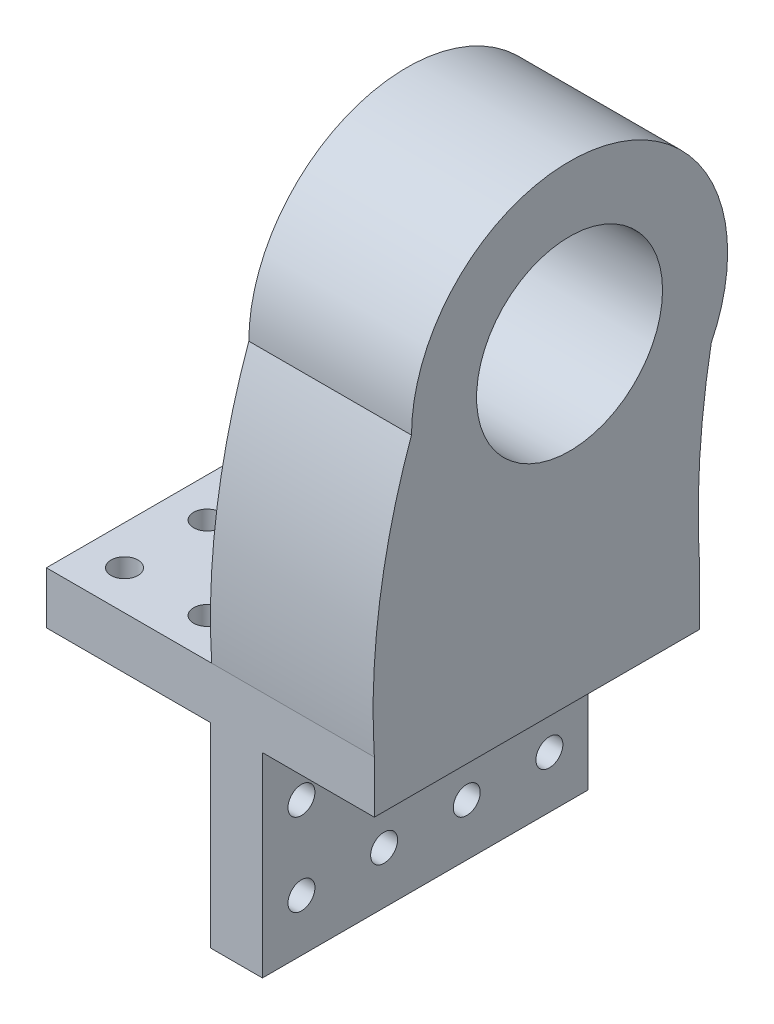
SolidWorks part; units mm, degrees
ref_plane "Alzado" through (0, 0, 0) normal (0, 0, 1) x (1, 0, 0)
ref_plane "Planta" through (0, 0, 0) normal (0, 1, 0) x (1, 0, 0)
ref_plane "Vista lateral" through (0, 0, 0) normal (1, 0, 0) x (0, 0, -1)
sketch "Croquis1" plane through (0, 0, 0) normal (0, 1, 0) x (1, 0, 0)
  line L1 (-25.2, -25) -> (25.2, -25)
  line L2 (-25.2, -25) -> (-25.2, 25)
  line L3 (-25.2, 25) -> (25.2, 25)
  line L4 (25.2, -25) -> (25.2, 25)
  line L5 (-25.2, -25) -> (25.2, 25) construction
  line L6 (-25.2, 25) -> (25.2, -25) construction
  point P0 (0, 0)
  dimension "D1" = 50.4
  dimension "D2" = 50
extrude "Saliente-Extruir1" add sketch "Croquis1" along normal blind 8
sketch "Croquis2" plane through (25.2, 0, 0) normal (1, 0, 0) x (0, 0, -1)
  line L0 (-25, 8) -> (25, 8) construction
  line L1 (-25, 8) -> (-25, 0) construction
  line L2 (-25, 8) -> (25, 8)
  circle A0 centre (5, 48) radius 14.29
  arc A1 (26.7814, 37.2494) -> (-19.29, 48) centre (5, 48) ccw
  arc A2 (-25, 8) -> (-19.29, 48) centre (74.8101, 14.1597) cw
  arc A3 (25, 8) -> (26.7814, 37.2494) centre (144.7726, 15.3844) cw
  dimension "D1" = 28.58
  dimension "D2" = 10
  dimension "D3" = 40
  dimension "D5" = 100
  dimension "D6" = 120
  dimension "D4" = 30
extrude "Saliente-Extruir2" add sketch "Croquis2" against normal blind 25
sketch "Croquis3" plane through (0, 0, 0) normal (0, -1, 0) x (1, 0, 0)
  line L0 (-25.2, 25) -> (25.2, 25) construction
  line L1 (0, 25) -> (8, 25)
  line L2 (0, 25) -> (0, -25)
  line L3 (0, -25) -> (8, -25)
  line L4 (8, 25) -> (8, -25)
  line L5 (25.2, -25) -> (-25.2, -25) construction
  dimension "D1" = 8
extrude "Saliente-Extruir3" add sketch "Croquis3" along normal blind 30
sketch "Croquis4" plane through (0, 8, 0) normal (0, 1, 0) x (1, 0, 0)
  line L0 (-25.2, -25) -> (0.2, -25) construction
  line L1 (-25.2, 25) -> (-25.2, -25) construction
  circle A0 centre (-19.2, -19) radius 2.07
  circle A1 centre (-19.2, -6.3) radius 2.07
  circle A2 centre (-19.2, 6.4) radius 2.07
  circle A3 centre (-19.2, 19.1) radius 2.07
  circle A4 centre (-6.5, -19) radius 2.07
  circle A5 centre (-6.5, 6.4) radius 2.07
  circle A6 centre (-6.5, -6.3) radius 2.07
  circle A7 centre (-6.5, 19.1) radius 2.07
  dimension "D1" = 4.14
  dimension "D2" = 6
  dimension "D3" = 6
  dimension "D4" = 4
  dimension "D5" = 2
extrude "Cortar-Extruir1" cut sketch "Croquis4" against normal through all
sketch "Croquis5" plane through (8, 0, 0) normal (1, 0, 0) x (0, 0, -1)
  line L0 (25, -30) -> (-25, -30) construction
  line L1 (-25, -30) -> (-25, 0) construction
  circle A0 centre (-19, -22) radius 2.07
  circle A1 centre (-6.3, -22) radius 2.07
  circle A2 centre (6.4, -22) radius 2.07
  circle A3 centre (19.1, -22) radius 2.07
  circle A4 centre (-19, -9.3) radius 2.07
  circle A5 centre (-6.3, -9.3) radius 2.07
  circle A6 centre (6.4, -9.3) radius 2.07
  circle A7 centre (19.1, -9.3) radius 2.07
  dimension "D1" = 4.14
  dimension "D2" = 8
  dimension "D3" = 6
  dimension "D4" = 4
  dimension "D5" = 2
extrude "Cortar-Extruir2" cut sketch "Croquis5" against normal blind 30
